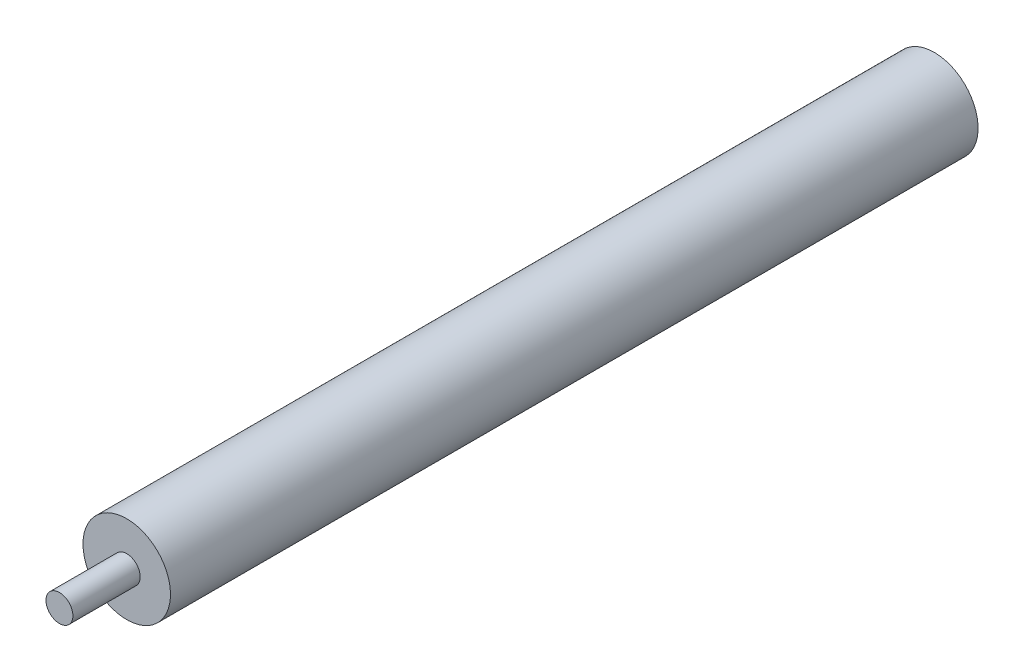
SolidWorks part; units mm, degrees
material "4032-T6"
ref_plane "Front Plane" through (0, 0, 0) normal (0, 0, 1) x (1, 0, 0)
ref_plane "Top Plane" through (0, 0, 0) normal (0, 1, 0) x (1, 0, 0)
ref_plane "Right Plane" through (0, 0, 0) normal (1, 0, 0) x (0, 0, -1)
sketch "Sketch1" plane through (0, 0, 0) normal (0, 0, 1) x (1, 0, 0)
  circle A0 centre (0, 0) radius 9.75
  dimension "D1" = 19.5
extrude "Boss-Extrude1" add sketch "Sketch1" along normal blind 180
sketch "Sketch2" plane through (0, 0, 180) normal (0, 0, 1) x (1, 0, 0)
  circle A0 centre (0, 0) radius 3
extrude "Boss-Extrude2" add sketch "Sketch2" along normal blind 15
